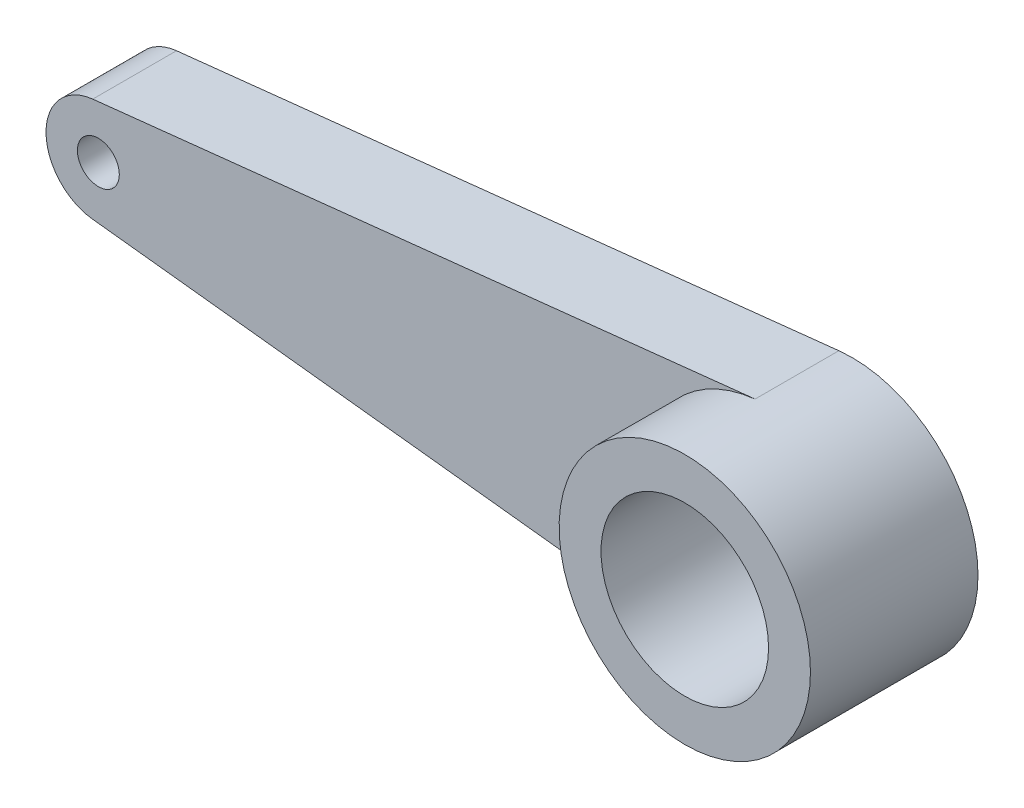
SolidWorks part; units mm, degrees
ref_plane "前视基准面" through (0, 0, 0) normal (0, 0, 1) x (1, 0, 0)
ref_plane "上视基准面" through (0, 0, 0) normal (0, 1, 0) x (1, 0, 0)
ref_plane "右视基准面" through (0, 0, 0) normal (1, 0, 0) x (0, 0, -1)
sketch "草图1" plane through (0, 0, 0) normal (0, 0, 1) x (1, 0, 0)
  line L1 (-16.1395, -1.2066) -> (-0.3348, -2.9813)
  line L2 (-16.134, 1.2784) -> (-0.3215, 2.9827)
  circle A0 centre (0, 0) radius 3
  circle A1 centre (0, 0) radius 2
  arc A2 (-16.134, 1.2784) -> (-16.1395, -1.2066) centre (-16, 0.0356) ccw
  circle A3 centre (-16, 0.0356) radius 0.5
  dimension "D1" = 6
  dimension "D3" = 2.5
  dimension "D5" = 1.25
  dimension "D9" = 1
  dimension "D4" = 16
  dimension "D6" = 3
  dimension "D7" = 1.25
  dimension "D8" = 3
  dimension "D2" = 1
extrude "凸台-拉伸1" add sketch "草图1" along normal blind 4 contours A0 A1 region at (-2.9151, 0.0065, 0)
extrude "凸台-拉伸2" add sketch "草图1<3>" along normal blind 2 contours L2 A2 L1 A0 A3 region at (-8.6198, 0.0192, 0)
sketch "草图1<3>" plane through (0, 0, 0) normal (0, 0, 1) x (1, 0, 0) same geometry as "草图1"
